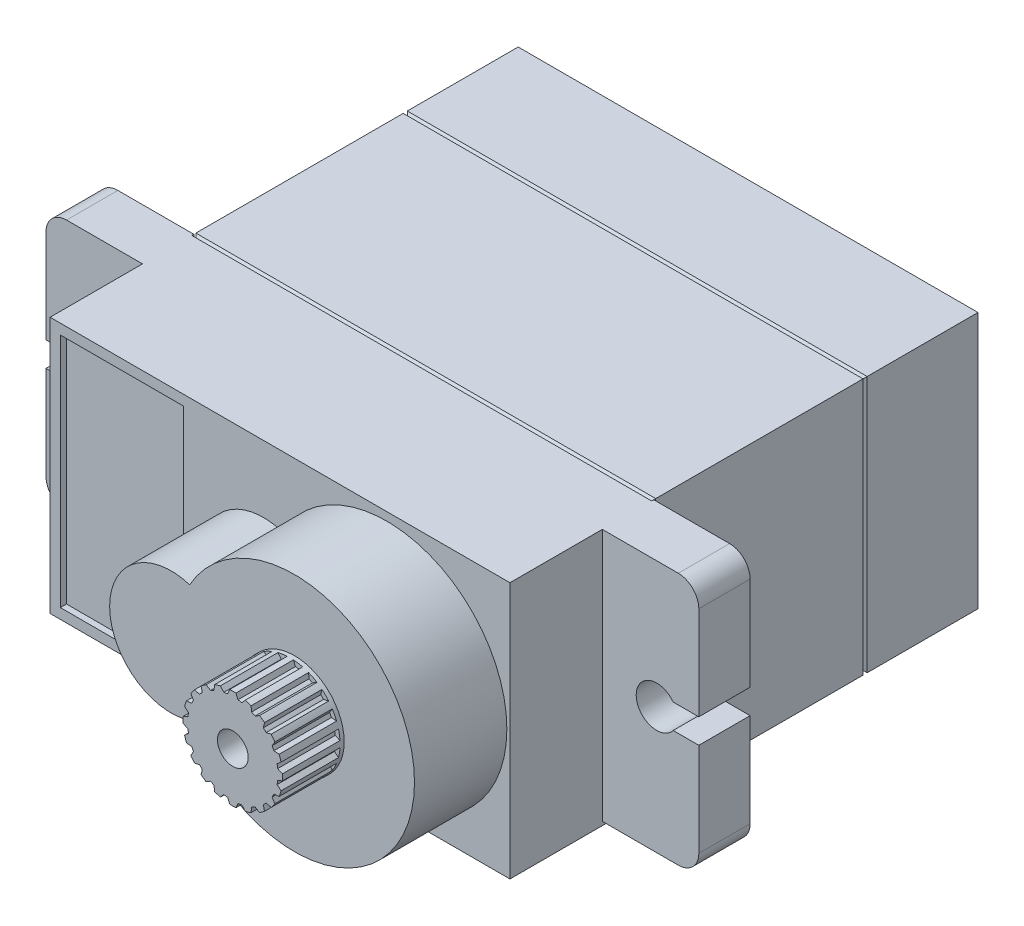
SolidWorks part; units mm, degrees
ref_plane "前视基准面" through (0, 0, 0) normal (0, 0, 1) x (1, 0, 0)
ref_plane "上视基准面" through (0, 0, 0) normal (0, 1, 0) x (1, 0, 0)
ref_plane "右视基准面" through (0, 0, 0) normal (1, 0, 0) x (0, 0, -1)
sketch "草图1" plane through (0, 0, 0) normal (0, 0, 1) x (1, 0, 0)
  line L1 (-11.2, 6.25) -> (11.2, 6.25)
  line L2 (-11.2, 6.25) -> (-11.2, -6.25)
  line L3 (-11.2, -6.25) -> (11.2, -6.25)
  line L4 (11.2, 6.25) -> (11.2, -6.25)
  dimension "D1" = 11.2
  dimension "D2" = 22.4
  dimension "D3" = 6.25
  dimension "D4" = 12.5
extrude "凸台-拉伸1" add sketch "草图1" along normal blind 5.5
chamfer "倒角1" distance 0.1 angle 45 4 edges at (0, 6.25, 5.5) (11.2, 0, 5.5) (0, -6.25, 5.5) (-11.2, 0, 5.5)
sketch "草图2" plane through (0, 0, 5.5) normal (0, 0, 1) x (1, 0, 0)
  line L0 (11.2, 6.25) -> (11.2, -6.25) construction
  line L1 (11.2, -6.25) -> (-11.2, -6.25) construction
  line L2 (-11.2, -6.25) -> (-11.2, 6.25) construction
  line L3 (-11.2, 6.25) -> (11.2, 6.25) construction
  line L12 (11.2, 6.25) -> (11.2, -6.25)
  line L13 (11.2, -6.25) -> (-11.2, -6.25)
  line L14 (-11.2, -6.25) -> (-11.2, 6.25)
  line L15 (-11.2, 6.25) -> (11.2, 6.25)
extrude "凸台-拉伸2" add sketch "草图2" along normal blind 10.3
chamfer "倒角2" distance 0.1 angle 45 4 edges at (0, 6.25, 5.5) (11.2, 0, 5.5) (0, -6.25, 5.5) (-11.2, 0, 5.5)
chamfer "倒角3" distance 0.1 angle 45 4 edges at (11.2, 0, 15.8) (0, -6.25, 15.8) (-11.2, 0, 15.8) (0, 6.25, 15.8)
sketch "草图3" plane through (0, 0, 15.8) normal (0, 0, 1) x (1, 0, 0)
  line L0 (11.2, 6.25) -> (11.2, -6.25) construction
  line L1 (11.2, -6.25) -> (-11.2, -6.25) construction
  line L2 (-11.2, -6.25) -> (-11.2, 6.25) construction
  line L3 (-11.2, 6.25) -> (11.2, 6.25) construction
  line L4 (11.2, 6.25) -> (11.2, -6.25)
  line L5 (11.2, -6.25) -> (-11.2, -6.25)
  line L6 (-11.2, -6.25) -> (-11.2, 6.25)
  line L7 (-11.2, 6.25) -> (11.2, 6.25)
extrude "凸台-拉伸3" add sketch "草图3" along normal blind 7
chamfer "倒角4" distance 0.1 angle 45 4 edges at (0, 6.25, 15.8) (11.2, 0, 15.8) (0, -6.25, 15.8) (-11.2, 0, 15.8)
ref_plane "基准面1" through (0, 0, 15.8) normal (0, 0, 1) x (1, 0, 0)
sketch "草图4" plane through (0, 0, 15.8) normal (0, 0, 1) x (1, 0, 0)
  line L0 (-15.9, -0.5083) -> (-15.9, -6.0667)
  line L1 (-11.2, 6.25) -> (-15.9, 6.25)
  line L2 (-11.2, 6.25) -> (-11.2, -6.0667)
  line L3 (-11.2, -6.0667) -> (-15.9, -6.0667)
  line L4 (-15.9, 6.25) -> (-15.9, 0.6917)
  line L6 (11.2, -6.0667) -> (15.9, -6.0667)
  line L7 (15.9, -0.5083) -> (14.65, -0.5083)
  line L8 (15.9, 0.6917) -> (14.65, 0.6917)
  line L9 (-15.9, -0.5083) -> (-14.65, -0.5083)
  line L10 (-15.9, 0.6917) -> (-14.65, 0.6917)
  line L11 (15.9, 6.25) -> (15.9, 0.6917)
  line L12 (11.2, 6.25) -> (11.2, -6.0667)
  line L13 (11.2, 6.25) -> (15.9, 6.25)
  line L14 (15.9, -0.5083) -> (15.9, -6.0667)
  arc A0 (-14.65, -0.5083) -> (-14.65, 0.6917) centre (-13.85, 0.0917) ccw
  arc A1 (14.65, -0.5083) -> (14.65, 0.6917) centre (13.85, 0.0917) cw
  point P19 (12.306, -0.5083)
  point P21 (12.306, 0.6917)
  dimension "D4" = 2
extrude "凸台-拉伸4" add sketch "草图4" along normal blind 2.5
sketch "草图5" plane through (0, 0, 22.8) normal (0, 0, 1) x (1, 0, 0)
  arc A0 (0.0981, -2.8624) -> (0.0981, 2.8624) centre (5.2, 0) ccw
  arc A1 (0.0981, 2.8624) -> (0.0981, -2.8624) centre (-0.8, 0) ccw
  dimension "D2" = 11.7
  dimension "D5" = 6
extrude "凸台-拉伸5" add sketch "草图5" along normal blind 4.5
sketch "草图6" plane through (0, 0, 27.3) normal (0, 0, 1) x (1, 0, 0)
  circle A0 centre (5.2, 0) radius 2.425
  dimension "D1" = 4.85
extrude "凸台-拉伸6" add sketch "草图6" along normal blind 3
sketch "草图7" plane through (0, 0, 30.3) normal (0, 0, 1) x (1, 0, 0)
  circle A0 centre (5.2, 0) radius 0.75
  dimension "D1" = 1.5
extrude "切除-拉伸1" cut sketch "草图7" against normal blind 6
sketch "草图8" plane through (0, 0, 30.3) normal (0, 0, 1) x (1, 0, 0)
  line L1 (4.95, 2.1857) -> (5.05, 2.4204)
  line L2 (5.45, 2.1857) -> (5.35, 2.4204)
  line L3 (6.1132, 2.0015) -> (6.0906, 2.2555)
  line L4 (5.6377, 2.156) -> (5.8053, 2.3482)
  line L5 (6.687, 1.6214) -> (6.744, 1.8699)
  line L6 (6.2825, 1.9153) -> (6.5013, 2.0463)
  line L7 (7.1153, 1.0825) -> (7.2463, 1.3013)
  line L8 (6.8214, 1.487) -> (7.0699, 1.544)
  line L9 (7.356, 0.4377) -> (7.5482, 0.6053)
  line L10 (7.2015, 0.9132) -> (7.4555, 0.8906)
  line L11 (7.3857, -0.25) -> (7.6204, -0.15)
  line L12 (7.3857, 0.25) -> (7.6204, 0.15)
  line L13 (7.2015, -0.9132) -> (7.4555, -0.8906)
  line L14 (7.356, -0.4377) -> (7.5482, -0.6053)
  line L15 (6.8214, -1.487) -> (7.0699, -1.544)
  line L16 (7.1153, -1.0825) -> (7.2463, -1.3013)
  line L17 (6.2825, -1.9153) -> (6.5013, -2.0463)
  line L18 (6.687, -1.6214) -> (6.744, -1.8699)
  line L19 (5.6377, -2.156) -> (5.8053, -2.3482)
  line L20 (6.1132, -2.0015) -> (6.0906, -2.2555)
  line L21 (4.95, -2.1857) -> (5.05, -2.4204)
  line L22 (5.45, -2.1857) -> (5.35, -2.4204)
  line L23 (4.2868, -2.0015) -> (4.3094, -2.2555)
  line L24 (4.7623, -2.156) -> (4.5947, -2.3482)
  line L25 (3.713, -1.6214) -> (3.656, -1.8699)
  line L26 (4.1175, -1.9153) -> (3.8987, -2.0463)
  line L27 (3.2847, -1.0825) -> (3.1537, -1.3013)
  line L28 (3.5786, -1.487) -> (3.3301, -1.544)
  line L29 (3.044, -0.4377) -> (2.8518, -0.6053)
  line L30 (3.1985, -0.9132) -> (2.9445, -0.8906)
  line L31 (3.0143, 0.25) -> (2.7796, 0.15)
  line L32 (3.0143, -0.25) -> (2.7796, -0.15)
  line L33 (3.1985, 0.9132) -> (2.9445, 0.8906)
  line L34 (3.044, 0.4377) -> (2.8518, 0.6053)
  line L35 (3.5786, 1.487) -> (3.3301, 1.544)
  line L36 (3.2847, 1.0825) -> (3.1537, 1.3013)
  line L37 (4.1175, 1.9153) -> (3.8987, 2.0463)
  line L38 (3.713, 1.6214) -> (3.656, 1.8699)
  line L39 (4.7623, 2.156) -> (4.5947, 2.3482)
  line L40 (4.2868, 2.0015) -> (4.3094, 2.2555)
  arc A0 (4.95, 2.1857) -> (4.7623, 2.156) centre (5.2, 0) ccw
  circle A1 centre (5.2, 0) radius 2.425 construction
  arc A2 (5.05, 2.4204) -> (4.5947, 2.3482) centre (5.2, 0) ccw
  arc A3 (4.2868, 2.0015) -> (4.1175, 1.9153) centre (5.2, 0) ccw
  arc A4 (4.3094, 2.2555) -> (3.8987, 2.0463) centre (5.2, 0) ccw
  arc A5 (5.6377, 2.156) -> (5.45, 2.1857) centre (5.2, 0) ccw
  arc A6 (5.8053, 2.3482) -> (5.35, 2.4204) centre (5.2, 0) ccw
  arc A7 (6.2825, 1.9153) -> (6.1132, 2.0015) centre (5.2, 0) ccw
  arc A8 (6.5013, 2.0463) -> (6.0906, 2.2555) centre (5.2, 0) ccw
  arc A9 (7.0699, 1.544) -> (6.744, 1.8699) centre (5.2, 0) ccw
  arc A10 (6.8214, 1.487) -> (6.687, 1.6214) centre (5.2, 0) ccw
  arc A11 (7.4555, 0.8906) -> (7.2463, 1.3013) centre (5.2, 0) ccw
  arc A12 (7.2015, 0.9132) -> (7.1153, 1.0825) centre (5.2, 0) ccw
  arc A13 (7.6204, 0.15) -> (7.5482, 0.6053) centre (5.2, 0) ccw
  arc A14 (7.3857, 0.25) -> (7.356, 0.4377) centre (5.2, 0) ccw
  arc A15 (7.5482, -0.6053) -> (7.6204, -0.15) centre (5.2, 0) ccw
  arc A16 (7.356, -0.4377) -> (7.3857, -0.25) centre (5.2, 0) ccw
  arc A17 (7.2463, -1.3013) -> (7.4555, -0.8906) centre (5.2, 0) ccw
  arc A18 (7.1153, -1.0825) -> (7.2015, -0.9132) centre (5.2, 0) ccw
  arc A19 (6.744, -1.8699) -> (7.0699, -1.544) centre (5.2, 0) ccw
  arc A20 (6.687, -1.6214) -> (6.8214, -1.487) centre (5.2, 0) ccw
  arc A21 (6.0906, -2.2555) -> (6.5013, -2.0463) centre (5.2, 0) ccw
  arc A22 (6.1132, -2.0015) -> (6.2825, -1.9153) centre (5.2, 0) ccw
  arc A23 (5.35, -2.4204) -> (5.8053, -2.3482) centre (5.2, 0) ccw
  arc A24 (5.45, -2.1857) -> (5.6377, -2.156) centre (5.2, 0) ccw
  arc A25 (4.5947, -2.3482) -> (5.05, -2.4204) centre (5.2, 0) ccw
  arc A26 (4.7623, -2.156) -> (4.95, -2.1857) centre (5.2, 0) ccw
  arc A27 (3.8987, -2.0463) -> (4.3094, -2.2555) centre (5.2, 0) ccw
  arc A28 (4.1175, -1.9153) -> (4.2868, -2.0015) centre (5.2, 0) ccw
  arc A29 (3.5786, -1.487) -> (3.713, -1.6214) centre (5.2, 0) ccw
  arc A30 (3.3301, -1.544) -> (3.656, -1.8699) centre (5.2, 0) ccw
  arc A31 (3.1985, -0.9132) -> (3.2847, -1.0825) centre (5.2, 0) ccw
  arc A32 (2.9445, -0.8906) -> (3.1537, -1.3013) centre (5.2, 0) ccw
  arc A33 (3.0143, -0.25) -> (3.044, -0.4377) centre (5.2, 0) ccw
  arc A34 (2.7796, -0.15) -> (2.8518, -0.6053) centre (5.2, 0) ccw
  arc A35 (3.044, 0.4377) -> (3.0143, 0.25) centre (5.2, 0) ccw
  arc A36 (2.8518, 0.6053) -> (2.7796, 0.15) centre (5.2, 0) ccw
  arc A37 (3.2847, 1.0825) -> (3.1985, 0.9132) centre (5.2, 0) ccw
  arc A38 (3.1537, 1.3013) -> (2.9445, 0.8906) centre (5.2, 0) ccw
  arc A39 (3.713, 1.6214) -> (3.5786, 1.487) centre (5.2, 0) ccw
  arc A40 (3.656, 1.8699) -> (3.3301, 1.544) centre (5.2, 0) ccw
  point P90 (5.2, 0)
  dimension "D1" = 4.4
extrude "切除-拉伸2" cut sketch "草图8" against normal blind 2.8
sketch "草图9" plane through (11.2, 0, 0) normal (1, 0, 0) x (0, 0, -1)
  line L0 (-5.5, -6.15) -> (-5.5, 6.15) construction
  circle A0 centre (-5.5, 0) radius 0.5
  circle A1 centre (-5.5, 1.2) radius 0.5
  circle A2 centre (-5.5, -1.2) radius 0.5
  dimension "D1" = 1
  dimension "D2" = 1.2
  dimension "D3" = 1
  dimension "D4" = 1
  dimension "D5" = 1.2
sketch "草图10" plane through (41.2, 0, 0) normal (1, 0, 0) x (0, 0, -1)
  line L3 (-6.95, 4.05) -> (-4.05, 4.05)
  line L4 (-6.95, 4.05) -> (-6.95, -4.05)
  line L5 (-6.95, -4.05) -> (-4.05, -4.05)
  line L6 (-4.05, 4.05) -> (-4.05, -4.05)
  dimension "D2" = 2.9
  dimension "D4" = 8.1
sketch "草图11" plane through (46.2, 0, 0) normal (1, 0, 0) x (0, 0, -1)
  line L5 (-6.0289, 2.95) -> (-4.8734, 2.95)
  line L6 (-6.0289, 2.95) -> (-6.0289, 2.15)
  line L7 (-6.0289, 2.15) -> (-4.8734, 2.15)
  line L16 (-6.45, 3.55) -> (-6.45, -3.55)
  line L17 (-6.45, -3.55) -> (-4.55, -3.55)
  line L18 (-4.55, -3.55) -> (-4.55, 3.55)
  line L19 (-4.55, 3.55) -> (-6.45, 3.55)
  line L20 (-6.45, 3.55) -> (-6.45, -3.55)
  line L21 (-6.45, -3.55) -> (-4.55, -3.55)
  line L22 (-4.55, -3.55) -> (-4.55, 3.55)
  line L23 (-4.55, 3.55) -> (-6.45, 3.55)
  line L24 (-4.8734, 2.95) -> (-4.8734, 2.15)
  line L25 (-6.0289, 0.35) -> (-4.8734, 0.35)
  line L26 (-6.0289, 0.35) -> (-6.0289, -0.45)
  line L27 (-6.0289, -0.45) -> (-4.8734, -0.45)
  line L28 (-4.8734, 0.35) -> (-4.8734, -0.45)
  line L29 (-6.0289, -2.25) -> (-4.8734, -2.25)
  line L30 (-6.0289, -2.25) -> (-6.0289, -3.05)
  line L31 (-6.0289, -3.05) -> (-4.8734, -3.05)
  line L32 (-4.8734, -2.25) -> (-4.8734, -3.05)
  dimension "D1" = 0.8
  dimension "D3" = 0.8
  dimension "D4" = 0.8
  dimension "D5" = 0.6
  dimension "D6" = 1.8
  dimension "D7" = 1.8
  dimension "D2" = 0.5
fillet "圆角2" radius 1 4 edges at (15.9, 6.25, 17.05) (15.9, -6.0667, 17.05) (-15.9, 6.25, 17.05) (-15.9, -6.0667, 17.05)
sketch "草图12" plane through (0, 0, 22.8) normal (0, 0, 1) x (1, 0, 0)
  line L0 (11.2, 6.25) -> (-11.2, 6.25) construction
  line L1 (-10.7, 5.75) -> (-4.7, 5.75)
  line L2 (-10.7, 5.75) -> (-10.7, -5.75)
  line L3 (-10.7, -5.75) -> (-4.7, -5.75)
  line L4 (-4.7, 5.75) -> (-4.7, -5.75)
  line L5 (-11.2, -6.25) -> (11.2, -6.25) construction
  line L6 (-11.2, -6.0667) -> (-11.2, 6.25) construction
  dimension "D1" = 6
  dimension "D2" = 0.5
  dimension "D3" = 0.5
  dimension "D4" = 0.5
extrude "切除-拉伸3" cut sketch "草图12" against normal blind 0.3
sketch "草图13" plane through (0, 0, 0) normal (0, 0, -1) x (-1, 0, 0)
  line L5 (-10.15, 5.7858) -> (-10.15, 5.15)
  line L6 (-9.85, -5.15) -> (-9.2142, -5.15)
  line L7 (-9.85, -4.85) -> (-9.2142, -4.85)
  line L8 (-9.85, 5.7858) -> (-9.85, 5.15)
  line L9 (-9.85, -4.85) -> (-9.85, -4.2142)
  line L10 (-10.15, -4.85) -> (-10.15, -4.2142)
  line L11 (-10.7858, -4.85) -> (-10.15, -4.85)
  line L12 (-10.7858, -5.15) -> (-10.15, -5.15)
  line L13 (-9.85, 4.85) -> (-9.85, 4.2142)
  line L14 (-9.85, 5.15) -> (-9.2142, 5.15)
  line L15 (-10.15, -5.7858) -> (-10.15, -5.15)
  line L16 (-10.15, 4.85) -> (-10.15, 4.2142)
  line L17 (-9.85, -5.7858) -> (-9.85, -5.15)
  line L18 (-9.85, 4.85) -> (-9.2142, 4.85)
  line L19 (9.85, -4.85) -> (9.2142, -4.85)
  line L20 (9.85, -5.15) -> (9.2142, -5.15)
  line L21 (9.85, -5.7858) -> (9.85, -5.15)
  line L22 (10.15, -5.7858) -> (10.15, -5.15)
  line L23 (10.7858, -5.15) -> (10.15, -5.15)
  line L24 (10.7858, -4.85) -> (10.15, -4.85)
  line L25 (-10.7858, 4.85) -> (-10.15, 4.85)
  line L26 (-10.7858, 5.15) -> (-10.15, 5.15)
  line L27 (10.15, -4.85) -> (10.15, -4.2142)
  line L28 (9.85, -4.85) -> (9.85, -4.2142)
  line L29 (10.15, 5.7858) -> (10.15, 5.15)
  line L30 (10.7858, 5.15) -> (10.15, 5.15)
  line L31 (10.7858, 4.85) -> (10.15, 4.85)
  line L32 (10.15, 4.85) -> (10.15, 4.2142)
  line L33 (9.85, 4.85) -> (9.85, 4.2142)
  line L34 (9.85, 4.85) -> (9.2142, 4.85)
  line L35 (9.85, 5.15) -> (9.2142, 5.15)
  line L36 (9.85, 5.7858) -> (9.85, 5.15)
  circle A1 centre (-10, 5) radius 1
  arc A2 (-10.7858, 5.15) -> (-10.7858, 4.85) centre (-10, 5) ccw
  arc A3 (-9.85, 5.7858) -> (-10.15, 5.7858) centre (-10, 5) ccw
  arc A4 (-9.2142, 4.85) -> (-9.2142, 5.15) centre (-10, 5) ccw
  arc A5 (-10.15, 4.2142) -> (-9.85, 4.2142) centre (-10, 5) ccw
  arc A6 (-9.2142, -4.85) -> (-9.2142, -5.15) centre (-10, -5) cw
  arc A7 (-10.15, -4.2142) -> (-9.85, -4.2142) centre (-10, -5) cw
  arc A8 (-10.7858, -5.15) -> (-10.7858, -4.85) centre (-10, -5) cw
  arc A9 (-9.85, -5.7858) -> (-10.15, -5.7858) centre (-10, -5) cw
  circle A10 centre (-10, -5) radius 1
  arc A11 (9.2142, -4.85) -> (9.2142, -5.15) centre (10, -5) ccw
  arc A12 (9.85, -5.7858) -> (10.15, -5.7858) centre (10, -5) ccw
  arc A13 (10.7858, -5.15) -> (10.7858, -4.85) centre (10, -5) ccw
  arc A14 (10.15, -4.2142) -> (9.85, -4.2142) centre (10, -5) ccw
  circle A15 centre (10, -5) radius 1
  arc A16 (10.7858, 5.15) -> (10.7858, 4.85) centre (10, 5) cw
  arc A17 (10.15, 4.2142) -> (9.85, 4.2142) centre (10, 5) cw
  arc A18 (9.2142, 4.85) -> (9.2142, 5.15) centre (10, 5) cw
  arc A19 (9.85, 5.7858) -> (10.15, 5.7858) centre (10, 5) cw
  circle A20 centre (10, 5) radius 1
  point P20 (-10.15, 6.25)
  point P21 (-10.15, -9.7753)
  point P22 (-11.2, 4.85)
  point P23 (14.1671, 4.85)
  point P24 (-9.85, 6.25)
  point P25 (-9.85, -9.7753)
  point P26 (-11.2, 5.15)
  point P27 (14.1671, 5.15)
  dimension "D5" = 2
  dimension "D6" = 1.6
extrude "凸台-拉伸10" add sketch "草图13" along normal blind 0.1
